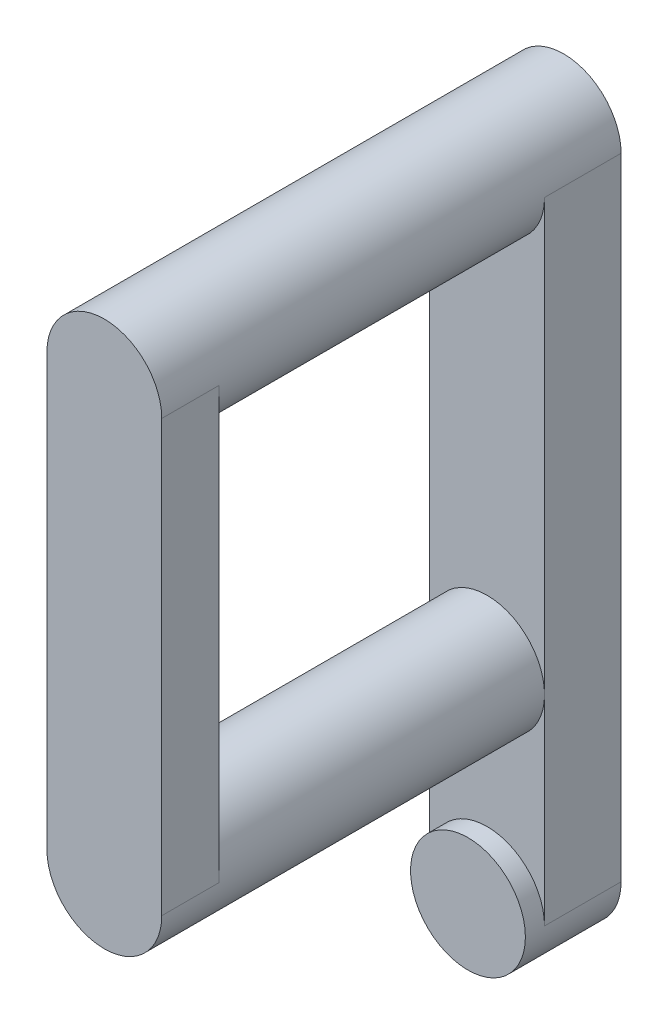
SolidWorks part; units mm, degrees
ref_plane "Ebene vorne" through (0, 0, 0) normal (0, 0, 1) x (1, 0, 0)
ref_plane "Ebene oben" through (0, 0, 0) normal (0, 1, 0) x (1, 0, 0)
ref_plane "Ebene rechts" through (0, 0, 0) normal (1, 0, 0) x (0, 0, -1)
sketch "Skizze1" plane through (0, 0, 0) normal (0, 0, 1) x (1, 0, 0)
  line L0 (40.5, -13.9439) -> (40.5, -46.9087) construction
  line L3 (43.5, -13.9439) -> (43.5, -46.9087)
  line L4 (37.5, -13.9439) -> (37.5, -46.9087)
  line L5 (35.5, -11.2293) -> (35.5, -43.1076) construction
  arc A2 (43.5, -13.9439) -> (37.5, -13.9439) centre (40.5, -13.9439) ccw
  arc A3 (37.5, -46.9087) -> (43.5, -46.9087) centre (40.5, -46.9087) ccw
  ellipse E0 centre (150.0617, -30.4263) end of major axis (33.1096, -30.4263) minor radius 40 (44.6781, -47.7721) -> (66.3, -58.3419) ccw construction
  ellipse E1 centre (150.0617, -30.4263) end of major axis (33.1096, -30.4263) minor radius 40 (58.5, -5.5403) -> (44.6781, -13.0805) ccw construction
  point P2 (40.5, -30.4263)
  dimension "D1" = 6
  dimension "D2" = 2
extrude "Aufsatz-Linear austragen1" add sketch "Skizze1" along normal blind 4
sketch "Skizze2" plane through (0, 0, 4) normal (0, 0, 1) x (1, 0, 0)
  line L0 (28.9801, -25.1939) -> (49.1308, -25.1939) construction
  circle A0 centre (40.5, -13.9439) radius 3
  arc A1 (43.5, -13.9439) -> (37.5, -13.9439) centre (40.5, -13.9439) ccw construction
  circle A2 centre (40.5, -36.4439) radius 3
  dimension "D1" = 22.5
extrude "Aufsatz-Linear austragen2" add sketch "Skizze2" along normal blind 20
sketch "Skizze3" plane through (0, 0, 24) normal (0, 0, 1) x (1, 0, 0)
  line L0 (40.5, -13.9439) -> (40.5, -36.4439) construction
  line L1 (43.5, -13.9439) -> (43.5, -36.4439)
  line L2 (37.5, -13.9439) -> (37.5, -36.4439)
  arc A0 (43.5, -13.9439) -> (37.5, -13.9439) centre (40.5, -13.9439) ccw
  arc A1 (37.5, -36.4439) -> (43.5, -36.4439) centre (40.5, -36.4439) ccw
  circle A2 centre (40.5, -13.9439) radius 3 construction
  arc A3 (37.5, -36.4439) -> (43.5, -36.4439) centre (40.5, -36.4439) ccw construction
  point P2 (40.5, -25.1939)
extrude "Aufsatz-Linear austragen3" add sketch "Skizze3" against normal blind 3
sketch "Skizze4" plane through (0, 0, 4) normal (0, 0, 1) x (1, 0, 0)
  circle A0 centre (40.5, -46.9087) radius 3
  arc A1 (37.5, -46.9087) -> (43.5, -46.9087) centre (40.5, -46.9087) ccw construction
extrude "Aufsatz-Linear austragen4" add sketch "Skizze4" along normal blind 5 from surface starting at face at (40.5, -30.4263, 0)
sketch "Skizze5" plane through (0, 0, 0) normal (0, 0, -1) x (-1, 0, 0)
  line L0 (-43.5, -30.4263) -> (-37.5, -30.4263) construction
  line L1 (-43.5, -46.9087) -> (-43.5, -13.9439) construction
  line L2 (-37.5, -13.9439) -> (-37.5, -46.9087) construction
  circle A0 centre (-40.5, -13.9439) radius 1.7
  circle A1 centre (-40.5, -46.9087) radius 1.7
  dimension "D1" = 3.4
extrude "Schnitt-Linear austragen1" cut sketch "Skizze5" against normal blind 4
equation "\"M2EinschmelzGewindeDurchmesser\"=3.4"
equation "\"M2EinschmelzGewindeTiefe\"= 4.0"
equation "\"M3EinschmelzGewindeDurchmesser\"= 4.2"
equation "\"M3EinschmelzGewindeTief\"= 5.7"
equation "\"M2SchraubeLoch\"=2.3"
equation "\"offSetVonGummiReifen\"= 3.0"
equation "\"D1@Skizze5\"=\"M2EinschmelzGewindeDurchmesser\""
equation "\"D1@Schnitt-Linear austragen1\"=\"M2EinschmelzGewindeTiefe\""
